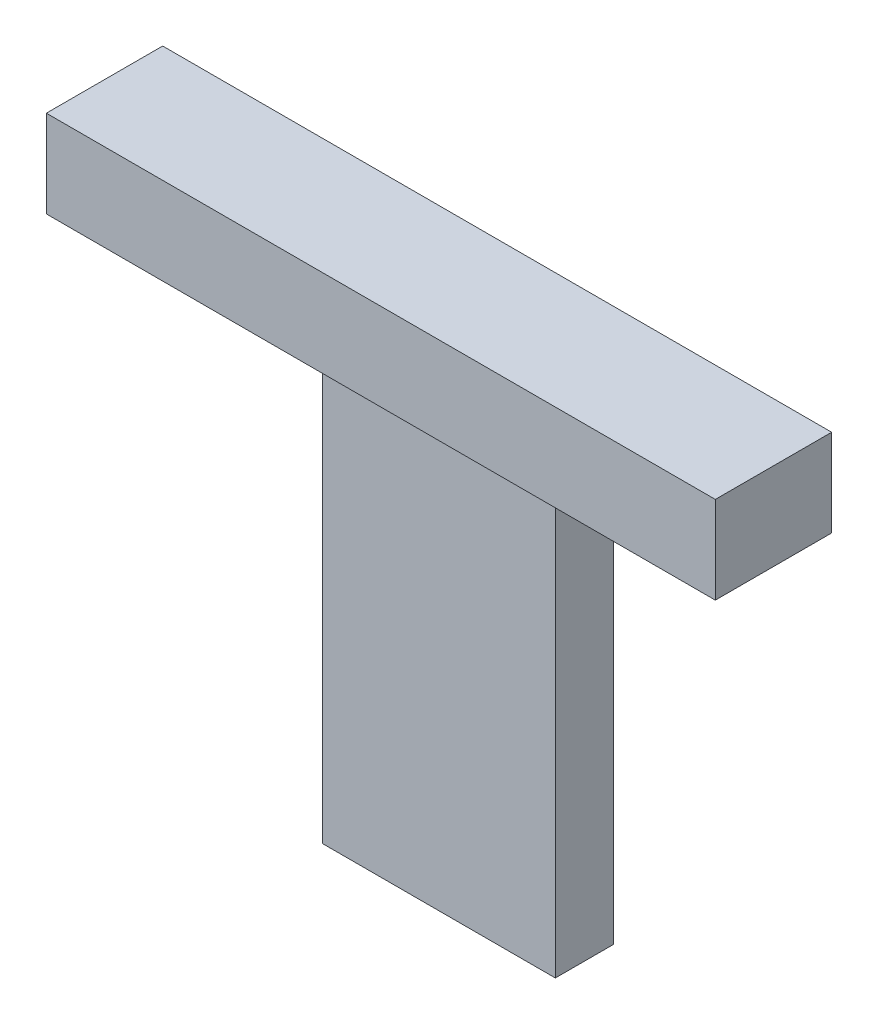
SolidWorks part; units mm, degrees
ref_plane "Front Plane" through (0, 0, 0) normal (0, 0, 1) x (1, 0, 0)
ref_plane "Top Plane" through (0, 0, 0) normal (0, 1, 0) x (1, 0, 0)
ref_plane "Right Plane" through (0, 0, 0) normal (1, 0, 0) x (0, 0, -1)
sketch "Sketch1" plane through (0, 0, 0) normal (0, 0, 1) x (1, 0, 0)
  line L0 (0, 80) -> (0, 95) construction
  line L1 (-40, -80) -> (40, -80)
  line L2 (-40, -80) -> (-40, 80)
  line L3 (-40, 80) -> (40, 80)
  line L4 (40, -80) -> (40, 80)
  line L5 (-40, -80) -> (40, 80) construction
  line L6 (-40, 80) -> (40, -80) construction
  line L8 (-115, 80) -> (115, 80)
  line L9 (-115, 80) -> (-115, 110)
  line L10 (-115, 110) -> (115, 110)
  line L11 (115, 80) -> (115, 110)
  line L12 (-115, 80) -> (115, 110) construction
  line L13 (-115, 110) -> (115, 80) construction
  point P0 (0, 0)
  dimension "D1" = 15
  dimension "D2" = 160
  dimension "D3" = 80
  dimension "D4" = 230
  dimension "D5" = 30
extrude "Boss-Extrude1" add sketch "Sketch1" along normal blind 20 contours L1 L4 L3 L2 region at (0, 0, 0)
extrude "Boss-Extrude2" add sketch "Sketch1<3>" along normal blind 40 contours L8 L11 L10 L9 L3 region at (0, 95, 0)
sketch "Sketch1<3>" plane through (0, 0, 0) normal (0, 0, 1) x (1, 0, 0) same geometry as "Sketch1"
